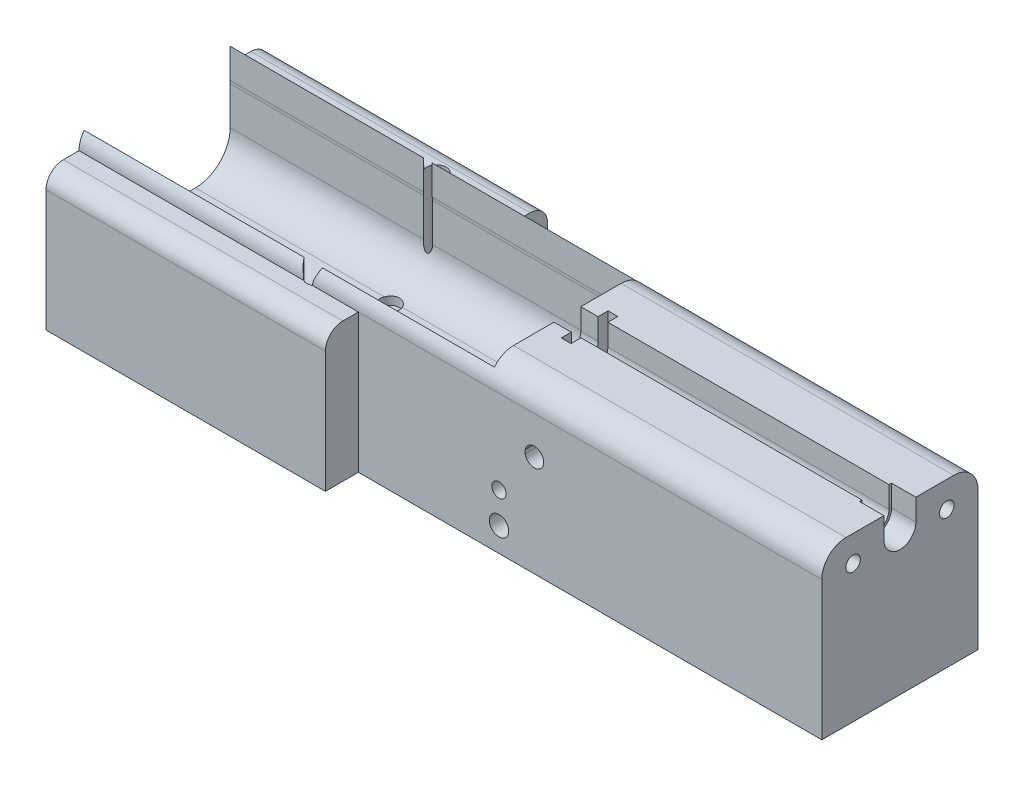
SolidWorks part; units mm, degrees
other "Markup1"
sketch "Sketch10" plane through (217, 42, -42) normal (0.057, 0.9883, -0.1416) x (-0.9984, 0.0574, -0.0017)
ref_plane "Front Plane" through (0, 0, 0) normal (0, 0, 1) x (1, 0, 0)
ref_plane "Top Plane" through (0, 0, 0) normal (0, 1, 0) x (1, 0, 0)
ref_plane "Right Plane" through (0, 0, 0) normal (1, 0, 0) x (0, 0, -1)
sketch "Sketch1" plane through (0, 0, 0) normal (0, 1, 0) x (1, 0, 0)
  line L1 (0, 0) -> (223, 0)
  line L2 (0, 0) -> (0, 45)
  line L3 (0, 45) -> (223, 45)
  line L4 (223, 0) -> (223, 45)
  dimension "D1" = 45
  dimension "D2" = 223
extrude "Boss-Extrude1" add sketch "Sketch1" along normal blind 42
sketch "Sketch7" plane through (0, 42, 0) normal (0, 1, 0) x (1, 0, 0)
  line L0 (223, 45) -> (0, 45) construction
  line L1 (9, 43.5) -> (127.2, 43.5)
  line L2 (9, 43.5) -> (9, 1.5)
  line L3 (9, 1.5) -> (127.2, 1.5)
  line L4 (127.2, 43.5) -> (127.2, 1.5)
  line L5 (0, 0) -> (223, 0) construction
  line L7 (0, 45) -> (0, 0) construction
  dimension "D1" = 1.5
  dimension "D2" = 1.5
  dimension "D3" = 9
  dimension "D4" = 118.2
extrude "Cut-Extrude17" cut sketch "Sketch7" against normal blind 21
sketch "Sketch4" plane through (223, 0, 0) normal (1, 0, 0) x (0, 0, -1)
  line L0 (0, 42) -> (45, 42) construction
  line L1 (18.625, 42) -> (26.375, 42)
  line L2 (18.625, 42) -> (18.625, 35.825)
  line L3 (18.625, 35.825) -> (26.375, 35.825)
  line L4 (26.375, 42) -> (26.375, 35.825)
  line L5 (0, 42) -> (0, 0) construction
  dimension "D4" = 6.175
  dimension "D1" = 0
  dimension "D2" = 18.625
  dimension "D3" = 7.75
extrude "Cut-Extrude14" cut sketch "Sketch4" against normal blind 97.8
sketch "Sketch5" plane through (223, 0, 0) normal (1, 0, 0) x (0, 0, -1)
  line L2 (0, 42) -> (0, 0) construction
  line L4 (18.625, 35.825) -> (26.375, 35.825) construction
  circle A0 centre (22.5, 35.825) radius 3.875
  dimension "D1" = 0
  dimension "D2" = 22.5
extrude "Cut-Extrude15" cut sketch "Sketch5" against normal blind 97.8
sketch "Sketch11" plane through (0, 42, 0) normal (0, 1, 0) x (1, 0, 0)
  line L0 (127.2, 26.375) -> (127.2, 43.5) construction
  line L1 (132.2, 29.25) -> (135, 29.25)
  line L2 (132.2, 29.25) -> (132.2, 15.75)
  line L3 (132.2, 15.75) -> (135, 15.75)
  line L4 (135, 29.25) -> (135, 15.75)
  line L5 (223, 45) -> (0, 45) construction
  dimension "D1" = 5
  dimension "D2" = 13.5
  dimension "D3" = 15.75
  dimension "D4" = 2.8
extrude "Cut-Extrude19" cut sketch "Sketch11" against normal blind 11.5
sketch "Sketch52" plane through (223, 0, 0) normal (1, 0, 0) x (0, 0, -1)
  line L0 (17.9, 42) -> (17.9, 35.82)
  line L1 (0, 42) -> (18.625, 42) construction
  line L2 (26.375, 42) -> (45, 42) construction
  line L3 (27.1, 42) -> (27.1, 35.82)
  line L4 (0, 42) -> (0, 0) construction
  line L5 (17.9, 42) -> (27.1, 42)
  arc A0 (17.9, 35.82) -> (27.1, 35.82) centre (22.5, 35.82) ccw
  dimension "D1" = 9.2
  dimension "D2" = 17.9
extrude "Cut-Extrude43" cut sketch "Sketch52" against normal blind 7
sketch "Sketch53" plane through (223, 0, 0) normal (1, 0, 0) x (0, 0, -1)
  line L0 (0, 42) -> (17.9, 42) construction
  line L1 (27.1, 42) -> (45, 42) construction
  circle A0 centre (9, 34.5) radius 2.1
  circle A1 centre (36, 34.5) radius 2.1
  arc A2 (17.9, 35.82) -> (27.1, 35.82) centre (22.5, 35.82) ccw construction
  arc A3 (17.9, 35.82) -> (27.1, 35.82) centre (22.5, 35.82) ccw construction
  dimension "D2" = 7.5
  dimension "D4" = 13.5
  dimension "D5" = 4.2
  dimension "D1" = 7.5
  dimension "D3" = 13.5
extrude "Cut-Extrude44" cut sketch "Sketch53" against normal blind 95
sketch "Sketch68" plane through (127.2, 0, 0) normal (-1, 0, 0) x (0, 0, 1)
  circle A0 centre (-9, 34.5) radius 2.65
  circle A1 centre (-36, 34.5) radius 2.65
  dimension "D1" = 5.3
extrude "Cut-Extrude57" cut sketch "Sketch68" against normal blind 28.3
ref_plane "Front" through (0, 21, 0) normal (0, 1, 0) x (1, 0, 0)
ref_plane "Top" through (127.2, 0, 0) normal (-1, 0, 0) x (0, 0, 1)
ref_plane "Right" through (0, 0, -22.5) normal (0, 0, 1) x (1, 0, 0)
sketch "Sketch14" plane through (0, 0, 0) normal (0, -1, 0) x (1, 0, 0)
  line L0 (0, -45) -> (0, 0) construction
  line L1 (9, -54.5) -> (89.5, -54.5)
  line L2 (9, -54.5) -> (9, -45)
  line L3 (9, 9.5) -> (89.5, 9.5)
  line L4 (89.5, -54.5) -> (89.5, -45)
  line L5 (223, -45) -> (0, -45) construction
  line L6 (89.5, -45) -> (223, -45)
  line L7 (223, -45) -> (223, 0)
  line L8 (223, 0) -> (89.5, 0)
  line L9 (0, 0) -> (223, 0) construction
  line L10 (9, 0) -> (0, 0)
  line L11 (0, 0) -> (0, -45)
  line L12 (0, -45) -> (9, -45)
  line L13 (9, 0) -> (9, 9.5)
  line L14 (89.5, 0) -> (89.5, 9.5)
  point P6 (0, -22.5)
  dimension "D1" = 64
  dimension "D2" = 80.5
  dimension "D3" = 9
  dimension "D4" = 9.5
extrude "Boss-Extrude2" add sketch "Sketch14" along normal blind 5
sketch "Sketch42" plane through (0, 0, 0) normal (0, 1, 0) x (1, 0, 0)
  line L0 (89.5, 0) -> (89.5, -9.5)
  line L1 (9, 45) -> (89.5, 45)
  line L2 (9, 45) -> (9, 54.5)
  line L3 (9, 54.5) -> (89.5, 54.5)
  line L4 (89.5, 45) -> (89.5, 54.5)
  line L5 (89.5, -9.5) -> (9, -9.5)
  line L6 (9, -9.5) -> (9, 0)
  line L7 (9, 0) -> (89.5, 0)
extrude "Boss-Extrude3" add sketch "Sketch42" along normal blind 35
extrude "Cut-Extrude32" cut sketch "Sketch38" against normal blind 4.7
sketch "Sketch38" plane through (127.2, -5, -22.5) normal (0, -1, 0) x (0, 0, -1)
  circle A3 centre (23.5, -61.2) radius 3.1
  circle A6 centre (10, -61.2) radius 3.1
extrude "Cut-Extrude34" cut sketch "Sketch40" against normal blind 9
sketch "Sketch40" plane through (127.2, -5, -22.5) normal (0, -1, 0) x (0, 0, -1)
  circle A3 centre (0, -33.7) radius 5.5
extrude "Cut-Extrude35" cut sketch "Sketch41" against normal blind 4
sketch "Sketch41" plane through (127.2, -5, -22.5) normal (0, -1, 0) x (0, 0, -1)
  circle A3 centre (20, -73.2) radius 5.75
  circle A6 centre (-20, -73.2) radius 5.75
fillet "Fillet1" radius 7 2 edges at (111.5, 42, -45) (111.5, 42, 0)
fillet "Fillet7" radius 5 2 edges at (49.25, 35, -54.5) (49.25, 35, 9.5)
extrude "Cut-Extrude39" cut sketch "Sketch47" against normal blind 7
sketch "Sketch47" plane through (127.2, -0.3, -22.5) normal (0, -1, 0) x (0, 0, -1)
  circle A0 centre (23.5, -61.2) radius 1.5
  circle A1 centre (10, -61.2) radius 1.5
sketch "Sketch49" plane through (0, 6.7, 0) normal (0, -1, 0) x (1, 0, 0)
  circle A0 centre (66, -32.5) radius 2.8
  circle A1 centre (66, -46) radius 2.8
  dimension "D1" = 5.6
extrude "Cut-Extrude41" cut sketch "Sketch49" against normal blind 33
sketch "Sketch55" [suppressed] plane through (223, 0, 0) normal (1, 0, 0) x (0, 0, -1)
  line L0 (42, -2) -> (42, 28.52)
  line L2 (42, 28.52) -> (3, 28.52)
  line L3 (3, 28.52) -> (3, -2)
  line L4 (3, -2) -> (42, -2)
  line L5 (45, 35) -> (45, -5) construction
  line L6 (45, -5) -> (0, -5) construction
  line L7 (0, 35) -> (0, -5) construction
  arc A1 (17.9, 35.82) -> (27.1, 35.82) centre (22.5, 35.82) ccw construction
  dimension "D1" = 3
  dimension "D2" = 3
  dimension "D3" = 3
  dimension "D4" = 7.3
extrude "Cut-Extrude46" [suppressed] cut sketch "Sketch55" against normal blind 55
sketch "Sketch56" plane through (0, -5, 0) normal (0, -1, 0) x (1, 0, 0)
  line L0 (127.2, -9) -> (127.2, -19.4)
  line L1 (127.2, -19.4) -> (143, -19.4)
  line L2 (143, -19.4) -> (143, -9)
  line L3 (143, -9) -> (127.2, -9)
  line L4 (0, 0) -> (0, -45) construction
  line L5 (223, 0) -> (89.5, 0) construction
  dimension "D1" = 127.2
  dimension "D2" = 10.4
  dimension "D3" = 15.8
  dimension "D4" = 9
extrude "Cut-Extrude47" cut sketch "Sketch56" against normal blind 32.15
sketch "Sketch57" plane through (0, -5, 0) normal (0, -1, 0) x (1, 0, 0)
  line L6 (127.2, -9) -> (127.2, -19.4) construction
  line L7 (127.2, -9) -> (122.2, -9)
  line L8 (127.2, -9) -> (127.2, -19.4)
  line L9 (127.2, -19.4) -> (122.2, -19.4)
  line L10 (122.2, -9) -> (122.2, -19.4)
  line L11 (143, -9) -> (127.2, -9) construction
  line L12 (127.2, -19.4) -> (143, -19.4) construction
  dimension "D4" = 5
extrude "Cut-Extrude48" cut sketch "Sketch57" against normal blind 15
extrude "Cut-Extrude49" cut sketch "Sketch58" against normal blind 10
sketch "Sketch58" plane through (127.2, 21, 0) normal (0, 0, 1) x (0, -1, 0)
  line L6 (-2.6328, 15.65) -> (-3.6672, 15.65)
  line L7 (-3.6672, 10.35) -> (-2.6328, 10.35)
  circle A4 centre (19.05, 2.8) radius 2.8
  circle A6 centre (10.15, 2.8) radius 2.05
  arc A12 (-2.6328, 10.35) -> (-2.6328, 15.65) centre (-3.15, 13) ccw
  arc A13 (-3.6672, 15.65) -> (-3.6672, 10.35) centre (-3.15, 13) ccw
sketch "Sketch59" plane through (0, 0, -19.4) normal (0, 0, 1) x (1, 0, 0)
  line L2 (137.55, 24.6672) -> (137.55, 23.6328) construction
  circle A0 centre (130, 1.95) radius 1.5
  circle A1 centre (130, 10.85) radius 0.95
  circle A2 centre (140.2, 24.15) radius 1.5
  circle A3 centre (130, 1.95) radius 2.8 construction
  circle A4 centre (130, 10.85) radius 2.05 construction
  arc A7 (142.85, 24.6672) -> (137.55, 24.6672) centre (140.2, 24.15) ccw construction
  dimension "D1" = 3
  dimension "D2" = 1.9
  dimension "D3" = 2.65
  dimension "D4" = 3
  dimension "D5" = 1.2
extrude "Cut-Extrude50" cut sketch "Sketch59" against normal blind 6.5
sketch "Sketch62" plane through (0, 0, 0) normal (-1, 0, 0) x (0, 0, 1)
  line L0 (0, -5) -> (-45, -5)
  line L1 (-45, -5) -> (-45, 35)
  line L3 (-38, 42) -> (-7, 42)
  line L4 (-38, 42) -> (-7, 42) construction
  line L5 (0, 35) -> (0, -5)
  arc A0 (0, 35) -> (-7, 42) centre (-7, 35) ccw
  arc A1 (-45, 35) -> (-38, 42) centre (-38, 35) cw
  point P13 (0, 42)
  dimension "D1" = 7
extrude "Cut-Extrude51" cut sketch "Sketch62" against normal blind 9
extrude "Cut-Extrude52" cut sketch "Sketch63" along normal blind 118.2
sketch "Sketch63" plane through (127.2, 21, -22.5) normal (-1, 0, 0) x (0, 0, -1)
  line L12 (-10.9597, -18.9503) -> (11.0403, -18.9503)
  line L17 (21.0403, -8.9503) -> (21.0403, 2.0497)
  line L18 (11.0403, 12.0497) -> (-10.9597, 12.0497)
  line L19 (-20.9597, 2.0497) -> (-20.9597, -8.9503)
  arc A16 (11.0403, -18.9503) -> (21.0403, -8.9503) centre (11.0403, -8.9503) ccw
  arc A17 (21.0403, 2.0497) -> (11.0403, 12.0497) centre (11.0403, 2.0497) ccw
  arc A18 (-10.9597, 12.0497) -> (-20.9597, 2.0497) centre (-10.9597, 2.0497) ccw
  arc A19 (-20.9597, -8.9503) -> (-10.9597, -18.9503) centre (-10.9597, -8.9503) ccw
extrude "Cut-Extrude53" cut sketch "Sketch64" against normal blind 14
sketch "Sketch64" plane through (127.2, -5, -22.5) normal (0, -1, 0) x (0, 0, -1)
  circle A3 centre (-1, -71.2) radius 1.5
extrude "Cut-Extrude54" cut sketch "Sketch65" against normal blind 9.95
sketch "Sketch65" plane through (127.2, 8.9503, -22.5) normal (0, 1, 0) x (0, 0, 1)
  circle A1 centre (1, -71.2) radius 2.8
extrude "Cut-Extrude55" cut sketch "Sketch66" against normal blind 25
sketch "Sketch66" plane through (127.2, -5, -22.5) normal (0, -1, 0) x (0, 0, -1)
  circle A3 centre (-20, -52.2) radius 1.5
extrude "Cut-Extrude56" cut sketch "Sketch67" against normal blind 7
sketch "Sketch67" plane through (9, 21, -22.5) normal (-1, 0, 0) x (0, 0, -1)
  circle A3 centre (27, -9) radius 1.45
  circle A6 centre (27, 21) radius 1.45
  circle A9 centre (-27, 21) radius 1.45
  circle A12 centre (-27, -9) radius 1.45
extrude "Cut-Extrude58" cut sketch "Sketch69" against normal blind 41 from offset 4
sketch "Sketch69" plane through (127.2, -5, -22.5) normal (0, -1, 0) x (0, 0, -1)
  circle A0 centre (-20, -52.2) radius 2.8
